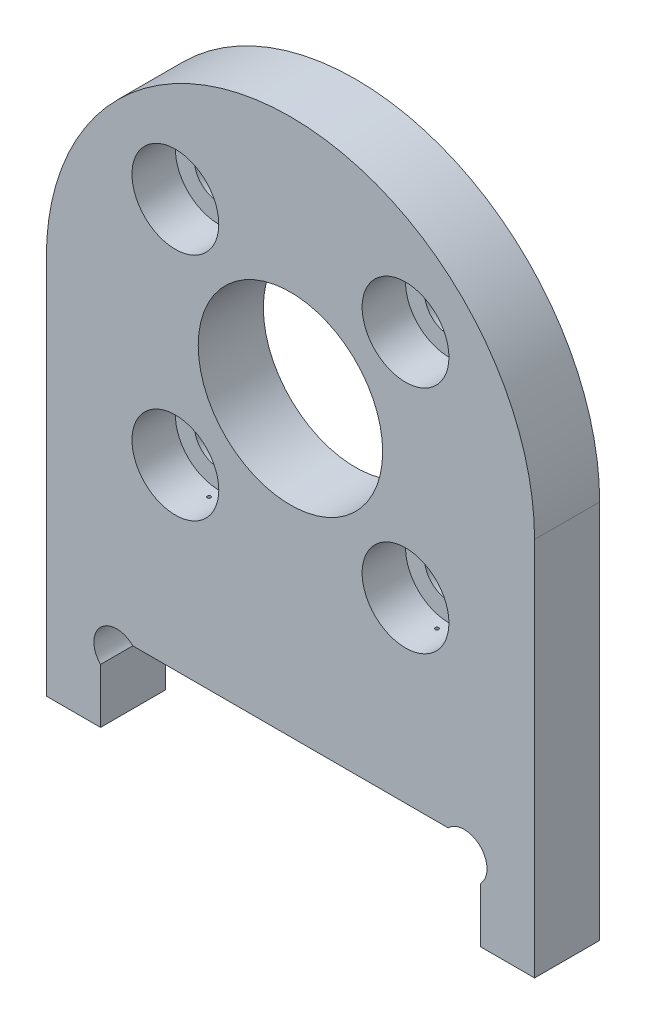
SolidWorks part; units mm, degrees
material "Сплав 2024"
ref_plane "Спереди" through (0, 0, 0) normal (0, 0, 1) x (1, 0, 0)
ref_plane "Сверху" through (0, 0, 0) normal (0, 1, 0) x (1, 0, 0)
ref_plane "Справа" through (0, 0, 0) normal (1, 0, 0) x (0, 0, -1)
sketch "Эскиз1" plane through (0, 0, 0) normal (0, 0, 1) x (1, 0, 0)
  line L0 (22.5, 0) -> (22.5, 62.6444) construction
  line L2 (0, 35) -> (0, 0)
  line L3 (0, 0) -> (45, 0)
  line L4 (45, 35) -> (45, 0)
  arc A1 (45, 35) -> (0, 35) centre (22.5, 35) ccw
  point P0 (0, 25)
  point P4 (20.0824, 6.1398)
  point P12 (24, 0)
  dimension "D1" = 22.5
  dimension "D4" = 45
  dimension "D2" = 35
extrude "Бобышка-Вытянуть1" add sketch "Эскиз1" along normal blind 6
sketch "Эскиз2" plane through (0, 0, 6) normal (0, 0, 1) x (1, 0, 0)
  circle A0 centre (22.5, 35) radius 8.5
  dimension "D1" = 17
extrude "Вырез-Вытянуть1" cut sketch "Эскиз2" against normal through all
sketch "Эскиз3" plane through (0, 0, 6) normal (0, 0, 1) x (1, 0, 0)
  line L0 (22.5, 35) -> (46.7565, 35) construction
  line L1 (38.3287, 50.8287) -> (-1.7457, 10.7543) construction
  line L2 (4.5263, 52.9737) -> (46.873, 10.627) construction
  circle A0 centre (22.5, 35) radius 15 construction
  dimension "D1" = 30
  dimension "D2" = 45
hole_wizard "Цековка для винта с внутренним шестигранником M41" positions "Эскиз5" profile "Эскиз4" counterbore size "M4" standard "Ansi Metric" end condition through all
sketch "Эскиз5" plane through (0, 0, 6) normal (0, 0, 1) x (1, 0, 0)
  line L0 (4.5263, 52.9737) -> (46.873, 10.627) construction
  line L1 (38.3287, 50.8287) -> (-1.7457, 10.7543) construction
  circle A0 centre (22.5, 35) radius 15 construction
  point P0 (11.8934, 45.6066)
  point P6 (33.1066, 45.6066)
  point P10 (33.1066, 24.3934)
  point P12 (11.8934, 24.3934)
sketch "Эскиз4" plane through (11.8934, 45.6066, 6) normal (1, 0, 0) x (0, -1, 0)
  line L0 (0, 0) -> (0, 6)
  line L1 (0, 6) -> (2.25, 6)
  line L3 (2.25, 6) -> (2.25, 4)
  line L4 (2.25, 4) -> (4, 4)
  line L5 (4, 4) -> (4, 0)
  line L7 (4, 0) -> (0, 0)
  line L11 (0, -6.35) -> (0, 107.95) construction
  dimension "Диаметр сквозного отверстия" = 4.5
  dimension "Глубина сквозного отверстия" = 6
  dimension "Диаметр цековки" = 8
  dimension "Глубина цековки" = 4
sketch "Эскиз6" plane through (0, 0, 6) normal (0, 0, 1) x (1, 0, 0)
  line L0 (0, 0) -> (45, 0) construction
  line L1 (5, 8) -> (40, 8)
  line L2 (5, 8) -> (5, -8)
  line L3 (5, -8) -> (40, -8)
  line L4 (40, 8) -> (40, -8)
  line L5 (5, 8) -> (40, -8) construction
  line L6 (5, -8) -> (40, 8) construction
  point P0 (22.5, 0)
  dimension "D1" = 35
  dimension "D2" = 16
extrude "Вырез-Вытянуть2" cut sketch "Эскиз6" against normal blind 10
sketch "Эскиз7" plane through (0, 8, 0) normal (0, -1, 0) x (1, 0, 0)
  line L0 (5, 3) -> (40, 3) construction
  line L1 (5, 0) -> (5, 6) construction
  line L2 (40, 6) -> (40, 0) construction
  line L3 (0, 6) -> (0, 0) construction
  line L4 (45, 6) -> (45, 0) construction
  point P6 (12, 3)
  point P7 (33, 3)
  dimension "D1" = 12
  dimension "D2" = 12
hole_wizard "Отверстие обработанное метчиком M4x0.71" positions "Эскиз9" profile "Эскиз8" tap size "M4x0.7" standard "Ansi Metric"
sketch "Эскиз9" plane through (0, 8, 0) normal (0, -1, 0) x (-1, 0, 0)
  point P0 (-12, -3)
  point P3 (-33, -3)
sketch "Эскиз8" plane through (12, 8, 3) normal (1, 0, 0) x (0, 0, -1)
  line L0 (0, 0) -> (0, 12.4914)
  line L1 (0, 12.4914) -> (1.65, 11.5)
  line L2 (1.65, 11.5) -> (1.65, 0)
  line L5 (1.65, 0) -> (0, 0)
  line L10 (0, 12.4914) -> (-1.65, 11.5) construction
  line L11 (0, -6.35) -> (0, 107.95) construction
  dimension "Диаметр сверла" = 3.3
  dimension "Глубина сверла" = 11.5
  dimension "Угол заточки сверла" = 118
cosmetic thread "Отверстие резьбы1" parameters "D1"=8, "D2"=4
cosmetic thread "Отверстие резьбы2" parameters "D1"=8, "D2"=4
sketch "Эскиз10" plane through (0, 0, 6) normal (0, 0, 1) x (1, 0, 0)
  line L0 (5, 8) -> (9.3059, 3.6941) construction
  line L1 (5, 8) -> (5, 0) construction
  line L2 (22.5, 8) -> (22.5, 5.7258) construction
  line L3 (40, 8) -> (5, 8) construction
  circle A0 centre (6.4849, 6.5151) radius 2.1
  circle A1 centre (38.5151, 6.5151) radius 2.1
  dimension "D1" = 4.2
  dimension "D2" = 45
extrude "Вырез-Вытянуть3" cut sketch "Эскиз10" against normal through all
